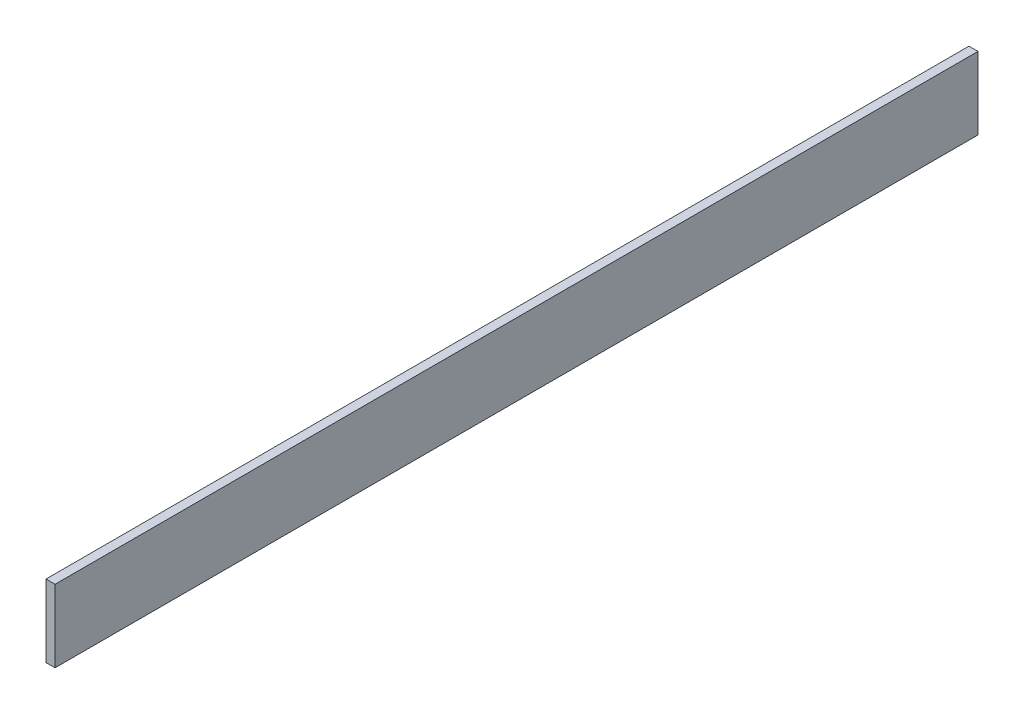
SolidWorks part; units mm, degrees
ref_plane "Front Plane" through (0, 0, 0) normal (0, 0, 1) x (1, 0, 0)
ref_plane "Top Plane" through (0, 0, 0) normal (0, 1, 0) x (1, 0, 0)
ref_plane "Right Plane" through (0, 0, 0) normal (1, 0, 0) x (0, 0, -1)
sketch "Sketch1" plane through (0, 0, 0) normal (1, 0, 0) x (0, 0, -1)
  line L1 (-647.7, -50.8) -> (647.7, -50.8)
  line L2 (-647.7, -50.8) -> (-647.7, 50.8)
  line L3 (-647.7, 50.8) -> (647.7, 50.8)
  line L4 (647.7, -50.8) -> (647.7, 50.8)
  line L5 (-647.7, -50.8) -> (647.7, 50.8) construction
  line L6 (-647.7, 50.8) -> (647.7, -50.8) construction
  point P0 (0, 0)
  dimension "D1" = 101.6
  dimension "D2" = 1295.4
extrude "Boss-Extrude1" add sketch "Sketch1" along normal blind 12.7
